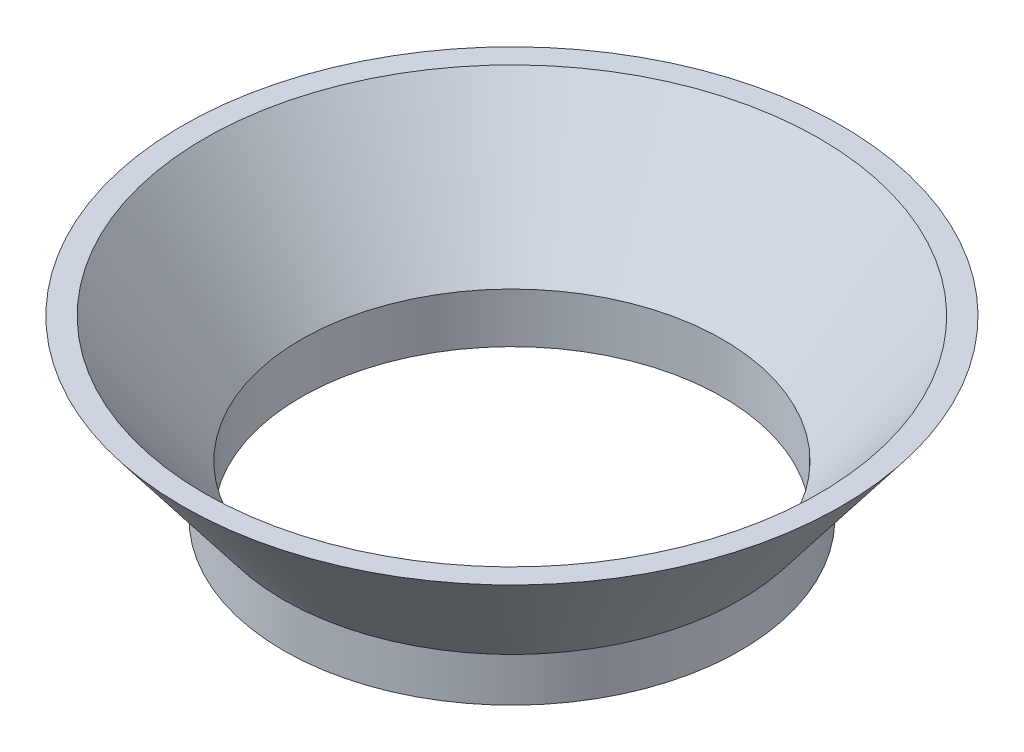
SolidWorks part; units mm, degrees
ref_plane "Front Plane" through (0, 0, 0) normal (0, 0, 1) x (1, 0, 0)
ref_plane "Top Plane" through (0, 0, 0) normal (0, 1, 0) x (1, 0, 0)
ref_plane "Right Plane" through (0, 0, 0) normal (1, 0, 0) x (0, 0, -1)
ref_axis "Axe1" through (0, 21, 0) along (0, -1, 0)
sketch "Esquisse1" plane through (0, 0, 0) normal (0, 0, 1) x (1, 0, 0)
  line L0 (26, 0) -> (26, 5)
  line L1 (26, 5) -> (37.5219, 20)
  line L2 (37.5219, 20) -> (35, 20)
  line L3 (35, 20) -> (24, 5.6795)
  line L4 (24, 5.6795) -> (24, 0)
  line L5 (24, 0) -> (26, 0)
  point P2 (8.6122, 0.1975)
  point P7 (0, 0)
  point P8 (26, 8.673)
  point P10 (25.9986, 5.0749)
  point P11 (26, 5)
  point P12 (40.1604, 20)
  dimension "D1" = 2
  dimension "D2" = 35
  dimension "D3" = 24
  dimension "D4" = 5
  dimension "D5" = 20
  dimension "D6" = 2
revolve "Révolution1" add sketch "Esquisse1" angle 360 about axis through (0, 21, 0) along (0, -1, 0)
